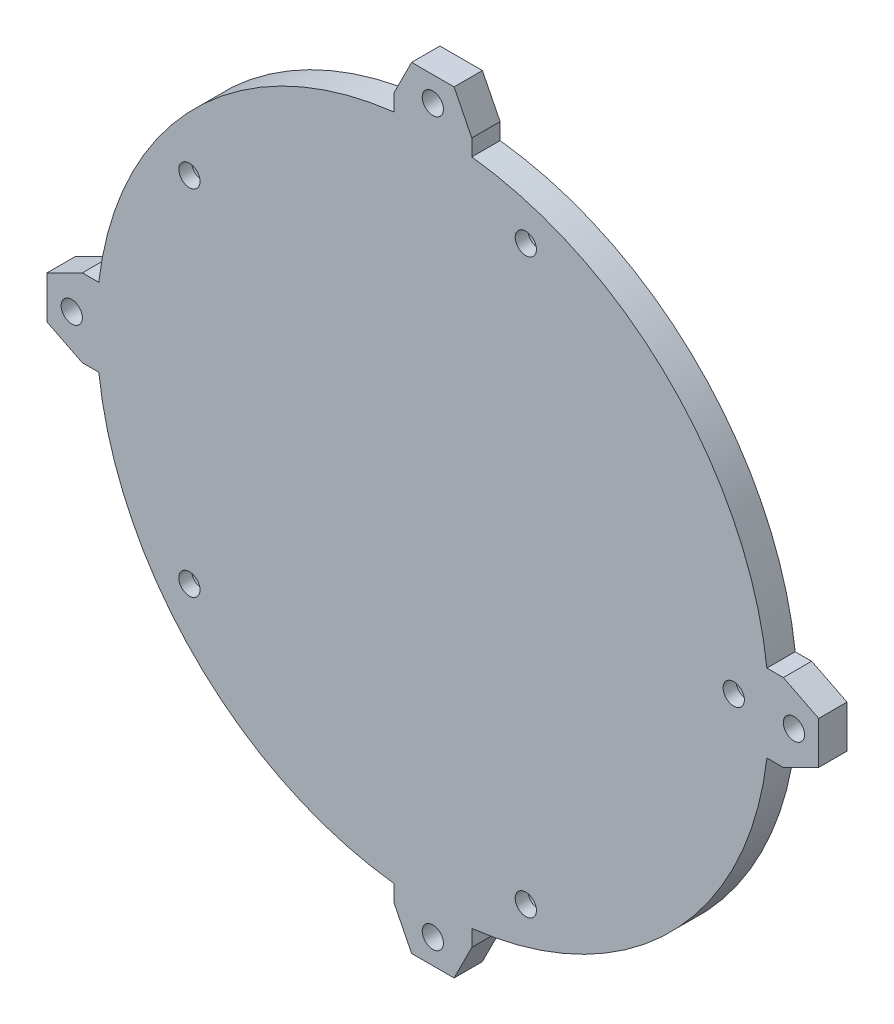
SolidWorks part; units mm, degrees
material "Beech"
ref_plane "Front Plane" through (0, 0, 0) normal (0, 0, 1) x (1, 0, 0)
ref_plane "Top Plane" through (0, 0, 0) normal (0, 1, 0) x (1, 0, 0)
ref_plane "Right Plane" through (0, 0, 0) normal (1, 0, 0) x (0, 0, -1)
sketch "Sketch1" plane through (0, 0, 0) normal (0, 0, 1) x (1, 0, 0)
  line L0 (51.5, 109) -> (57.5, 109)
  line L1 (60, 104) -> (57.5, 109)
  line L2 (51.5, 109) -> (49, 104)
  line L3 (49, 104) -> (49, 101.6805)
  line L4 (60, 104) -> (60, 101.6805)
  line L5 (109, 57.5) -> (109, 51.5)
  line L6 (104, 49) -> (109, 51.5)
  line L7 (109, 57.5) -> (104, 60)
  line L8 (104, 60) -> (101.6805, 60)
  line L9 (104, 49) -> (101.6805, 49)
  line L10 (0, 51.5) -> (0, 57.5)
  line L11 (5, 60) -> (0, 57.5)
  line L12 (0, 51.5) -> (5, 49)
  line L13 (5, 49) -> (7.3195, 49)
  line L14 (5, 60) -> (7.3195, 60)
  line L15 (57.5, 0) -> (51.5, 0)
  line L16 (49, 5) -> (51.5, 0)
  line L17 (57.5, 0) -> (60, 5)
  line L18 (60, 5) -> (60, 7.3195)
  line L19 (49, 5) -> (49, 7.3195)
  arc A0 (7.3195, 49) -> (49, 7.3195) centre (54.5, 54.5) ccw
  circle A1 centre (97, 54.5) radius 1.5
  circle A2 centre (67.6332, 94.9199) radius 1.5
  circle A3 centre (20.1168, 79.4809) radius 1.5
  circle A4 centre (20.1168, 29.5191) radius 1.5
  circle A5 centre (67.6332, 14.0801) radius 1.5
  circle A6 centre (54.5, 105.5) radius 1.5
  circle A7 centre (105.5, 54.5) radius 1.5
  circle A8 centre (3.5, 54.5) radius 1.5
  circle A9 centre (54.5, 3.5) radius 1.5
  arc A10 (49, 101.6805) -> (7.3195, 60) centre (54.5, 54.5) ccw
  arc A11 (101.6805, 60) -> (60, 101.6805) centre (54.5, 54.5) ccw
  arc A12 (60, 7.3195) -> (101.6805, 49) centre (54.5, 54.5) ccw
  circle A13 centre (20.1168, 79.4809) radius 2.75
  circle A14 centre (20.1168, 29.5191) radius 2.75
  circle A15 centre (67.6332, 94.9199) radius 2.75
  circle A16 centre (97, 54.5) radius 2.75
  circle A17 centre (67.6332, 14.0801) radius 2.75
extrude "Boss-Extrude2" add sketch "Sketch1" along normal blind 4 contours A13 A3 | L18 A12 L9 L6 L5 L7 L8 A11 L4 L1 L0 L2 L3 A10 L14 L11 L10 L12 L13 A0 L19 L16 L15 L17 A17 A16 A15 A14 A13 A6 A7 A8 A9 | A15 A2 | A16 A1 | A17 A5 | A14 A4 region at (54.5, 54.5, 0) region at (17.4446, 79.4809, 0) region at (17.4446, 29.5191, 0) region at (64.961, 94.9199, 0) region at (94.3278, 54.5, 0) region at (64.961, 14.0801, 0)
extrude "Cut-Extrude1" cut sketch "Sketch1<4>" along normal blind 2.2 contours A14 A4 | A17 A5 | A16 A1 | A15 A2 | A13 A3 region at (17.4446, 79.4809, 0) region at (17.4446, 29.5191, 0) region at (64.961, 94.9199, 0) region at (94.3278, 54.5, 0) region at (64.961, 14.0801, 0)
sketch "Sketch1<4>" plane through (0, 0, 0) normal (0, 0, 1) x (1, 0, 0) same geometry as "Sketch1"
